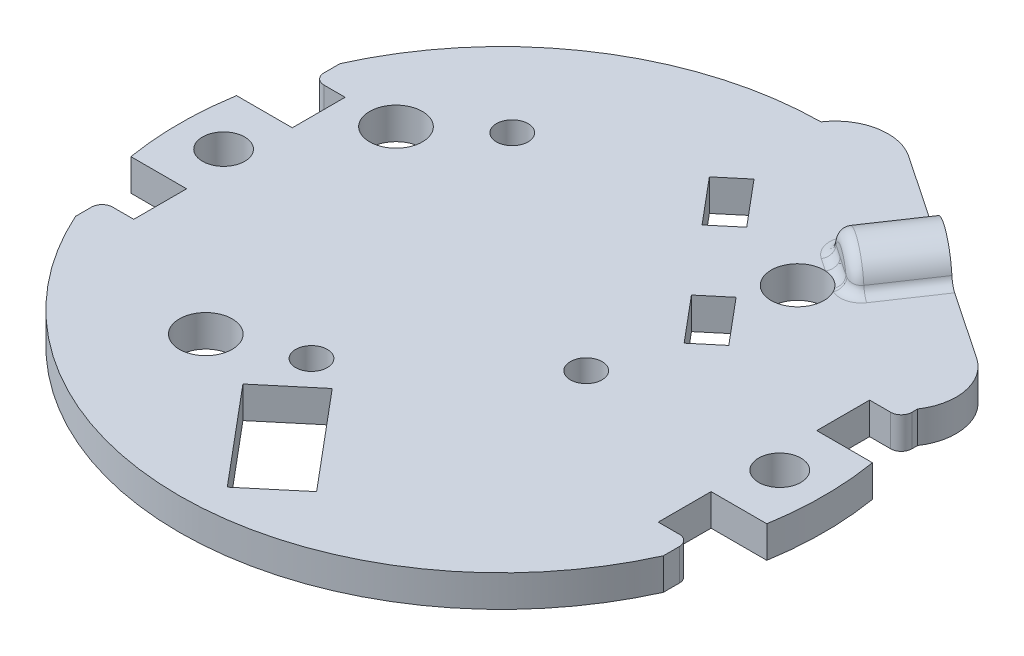
SolidWorks part; units mm, degrees
ref_plane "Alzado" through (0, 0, 0) normal (0, 0, 1) x (1, 0, 0)
ref_plane "Planta" through (0, 0, 0) normal (0, 1, 0) x (1, 0, 0)
ref_plane "Vista lateral" through (0, 0, 0) normal (1, 0, 0) x (0, 0, -1)
sketch "Croquis1" plane through (0, 0, 0) normal (0, 1, 0) x (1, 0, 0)
  circle A0 centre (0, 0) radius 30.5
extrude "Saliente-Extruir1" add sketch "Croquis1" along normal blind 3
sketch "Croquis5" plane through (0, 3, 0) normal (0, 1, 0) x (1, 0, 0)
  line L0 (0, 0) -> (0, 10)
  line L1 (28.8141, -5) -> (30.0874, -5)
  line L2 (28.8141, 5) -> (30.0874, 5)
  line L3 (-24.8141, 10) -> (-28.8141, 10)
  line L4 (24.8141, -5) -> (24.8141, -10)
  line L5 (-24.8141, -10) -> (-28.8141, -10)
  line L6 (24.8141, -5) -> (28.8141, -5)
  line L7 (24.8141, 5) -> (24.8141, 10)
  line L8 (-24.8141, 5) -> (-28.8141, 5)
  line L9 (-24.8141, 5) -> (-24.8141, 10)
  line L10 (-24.8141, -5) -> (-28.8141, -5)
  line L11 (-24.8141, -5) -> (-24.8141, -10)
  line L12 (24.8141, 5) -> (28.8141, 5)
  line L13 (24.8141, -10) -> (28.8141, -10)
  line L14 (24.8141, 10) -> (28.8141, 10)
  line L15 (-28.8141, 5) -> (-30.0874, 5)
  line L16 (-28.8141, -5) -> (-30.0874, -5)
  circle A1 centre (0, 0) radius 30.5 construction
  arc A2 (-28.8141, 10) -> (-30.0874, 5) centre (0, 0) ccw
  arc A3 (28.8141, 10) -> (28.8141, -10) centre (0, 0) cw
  arc A4 (-30.0874, -5) -> (-28.8141, -10) centre (0, 0) ccw
  arc A5 (30.0874, -5) -> (28.8141, -10) centre (0, 0) cw
  arc A6 (28.8141, 10) -> (30.0874, 5) centre (0, 0) cw
  circle M2 centre (0, 0) radius 30.5
extrude "Cortar-Extruir3" cut sketch "Croquis5" against normal blind 4 contours L11 L10 L8 L9 L3 L5 M2 | L15 L8 L9 L3 M2 | L14 L7 L12 L2 M2 | L4 L13 L1 L6 M2 region at (27.1844, 3, 7.3876) region at (27.1844, 3, -7.3876) region at (-27.1844, 3, 7.3876) region at (-27.1844, 3, -7.3876)
sketch "Croquis7" plane through (0, 3, 0) normal (0, 1, 0) x (1, 0, 0)
  line L0 (-8.1011, 29.1011) -> (9.5756, 8.0348)
  line L1 (9.5756, 8.0348) -> (27.2522, -13.0314)
  line L2 (-8.1011, 29.1011) -> (-27.2522, 13.0314)
  line L3 (27.2522, -13.0314) -> (8.1011, -29.1011)
  line L4 (8.1011, -29.1011) -> (-27.2522, 13.0314)
  line L5 (1.4284, 22.4114) -> (-0.8697, 20.4831)
  line L6 (1.4284, 22.4114) -> (4.6423, 18.5812)
  line L7 (4.6423, 18.5812) -> (2.3442, 16.6528)
  line L8 (2.3442, 16.6528) -> (-0.8697, 20.4831)
  line L9 (7.9686, 9.95) -> (11.1825, 6.1197)
  line L10 (8.1011, -29.1011) -> (5.53, -26.0369)
  line L11 (10.2667, 11.8783) -> (13.4807, 8.0481)
  line L12 (13.4807, 8.0481) -> (11.1825, 6.1197)
  line L13 (10.2667, 11.8783) -> (7.9686, 9.95)
  line L14 (5.53, -26.0369) -> (10.8923, -21.5374)
  line L15 (10.8923, -21.5374) -> (-19.3188, 14.4667)
  line L17 (-24.6811, 9.9672) -> (-19.3188, 14.4667)
  point P7 (-9.5756, -8.0348)
extrude "Cortar-Extruir5" cut sketch "Croquis7" against normal blind 4 contours L7 L6 L5 L0 | L11 L13 L0 L1 L12 region at (1.8863, 3, -19.5321) region at (10.7246, 3, -8.999)
sketch "Croquis8" plane through (0, 3, 0) normal (0, 1, 0) x (1, 0, 0)
  line L0 (-11.3137, 11.3137) -> (0, 0)
  line L2 (0, 0) -> (12, 0)
  line L3 (0, 0) -> (-11.3137, 11.3137)
  line L4 (12, 0) -> (12, 16)
  line L5 (0, 0) -> (-12, 0)
  line L6 (-12, 0) -> (-12, -16)
  line L10 (1.5586, -27.5246) -> (6.1549, -23.6679)
  line L11 (6.1549, -23.6679) -> (-1.5586, -14.4754)
  line L13 (-6.1549, -18.3321) -> (-1.5586, -14.4754)
  line L14 (1.5586, -27.5246) -> (-6.1549, -18.3321)
  circle A0 centre (0, 0) radius 30
  circle A1 centre (9, -1) radius 1.5
  circle A2 centre (-5, -13) radius 1.5
  circle A3 centre (-12, -16) radius 2.5
  circle A4 centre (-14, 15) radius 1.5
  circle A5 centre (12, 16) radius 2.5
  point P20 (-3.8567, -16.4037)
extrude "Cortar-Extruir6" cut sketch "Croquis8" against normal blind 10 contours L13 L10 L11 | A3 | L6 A3 | A3 L6 | A5 | L4 A5 | A5 L4 | L14 L10 L11 | L14 L11 | L13 L11 | A4 | L2 A1 | L2 A1 | A2 region at (10.2822, 3, -17.7178) region at (9, 3, -0.2032) region at (9, 3, 1.148) region at (-10.2822, 3, 14.2822) region at (0, 3, 21) region at (-5, 3, 13) region at (-14, 3, -15)
sketch "Croquis10" plane through (0, 3, 0) normal (0, 1, 0) x (1, 0, 0)
  line L0 (-24.8141, 10) -> (-27.8141, 10)
  line L2 (-24.8141, 10) -> (-28.8141, 10) construction
  line L4 (-27.8141, 10) -> (-27.8141, 12.5151)
  line L6 (-27.8141, 10) -> (-28.8141, 10)
  line L14 (-27.8141, -10) -> (-28.8141, -10)
  line L15 (-27.8141, -10) -> (-27.8141, -12.5151)
  line L16 (27.8141, -10) -> (27.8141, -12.5151)
  line L17 (27.8141, -10) -> (28.8141, -10)
  line L21 (27.8141, 10) -> (28.8141, 10)
  line L22 (27.8141, 10) -> (27.8141, 12.5151)
  line L23 (24.8141, 10) -> (27.8141, 10)
  circle A0 centre (-26.3141, 0) radius 2
  circle A1 centre (26.3141, 0) radius 2
  arc A2 (28.8141, 10) -> (-28.8141, 10) centre (0, 0) ccw construction
  arc A5 (-27.8141, 12.5151) -> (-28.8141, 10) centre (0, 0) ccw
  arc A7 (-27.8141, -12.5151) -> (-28.8141, -10) centre (0, 0) cw
  arc A8 (27.8141, -12.5151) -> (28.8141, -10) centre (0, 0) ccw
  arc A10 (27.8141, 12.5151) -> (28.8141, 10) centre (0, 0) cw
  line M13 (24.8141, 10) -> (28.8141, 10)
  arc M14 (28.8141, 10) -> (-28.8141, 10) centre (0, 0) ccw
  line M15 (-28.8141, 10) -> (-24.8141, 10)
  line M21 (-24.8141, -10) -> (-28.8141, -10)
  arc M22 (-28.8141, -10) -> (28.8141, -10) centre (0, 0) ccw
  line M23 (28.8141, -10) -> (24.8141, -10)
extrude "Cortar-Extruir8" cut sketch "Croquis10" against normal blind 3 contours L15 M21 M22 | L4 M15 M14 | L16 M23 M22 | L22 M13 M14 | A0 | A1 | L22 A10 L21 region at (-28.1547, 3, -10.8559) region at (28.1547, 3, -10.8559) region at (-28.1547, 3, 10.8559) region at (28.1547, 3, 10.8559) region at (-26.3141, 3, 0) region at (26.3141, 3, 0)
sketch "Croquis11" plane through (0, 3, 0) normal (0, 1, 0) x (1, 0, 0)
  line L0 (0, 0) -> (-20, 0)
  line L1 (-20, 0) -> (-20, 10)
  line L2 (0, 0) -> (0, 4.5949)
  line L3 (29.8013, 10.2046) -> (-1.7022, 31.454)
  circle A0 centre (-20, 10) radius 2.5
  circle A5 centre (0, 0) radius 31.5
  line M20 (27.8141, 10) -> (27.8141, 12.5151)
  arc M21 (27.8141, 12.5151) -> (-27.8141, 12.5151) centre (0, 0) ccw
extrude "Cortar-Extruir9" cut sketch "Croquis11" against normal blind 3 contours L3 M20 M21 | A0 region at (15.2326, 3, -22.6507) region at (-18.2822, 3, -8.2822)
sketch "Croquis13" plane through (14.0495, 0, -20.8293) normal (0.5592, 0, -0.829) x (-0.829, 0, -0.5592)
  line L1 (-16.603, 0) -> (17.2916, 0)
  line L2 (-16.603, 0) -> (-16.603, 3)
  line L3 (-16.603, 3) -> (17.2916, 3)
  line L4 (17.2916, 0) -> (17.2916, 3)
extrude "Saliente-Extruir2" add sketch "Croquis13" along normal blind 6
sketch "Croquis14" plane through (17.4047, 0, -25.8035) normal (0.5592, 0, -0.829) x (-0.829, 0, -0.5592)
  circle A0 centre (0.0043, 3) radius 3
extrude "Saliente-Extruir3" add sketch "Croquis14" against normal blind 8
sketch "Croquis17" plane through (17.4047, 0, -25.8035) normal (0.5592, 0, -0.829) x (-0.829, 0, -0.5592)
  circle A0 centre (0.0043, 3) radius 1.5
extrude "Cortar-Extruir10" cut sketch "Croquis17" against normal blind 7
sketch "Croquis19" plane through (17.4047, 0, -25.8035) normal (0.5592, 0, -0.829) x (-0.829, 0, -0.5592)
  line L0 (3.0043, 3) -> (17.2916, 3)
  line L1 (17.2916, 3) -> (17.2916, 0)
  line L2 (17.2916, 0) -> (-16.603, 0)
  line L3 (-16.603, 0) -> (-16.603, 3)
  line L4 (-16.603, 3) -> (-2.9957, 3)
  arc A0 (3.0043, 3) -> (-2.9957, 3) centre (0.0043, 3) ccw
extrude "Cortar-Extruir11" cut sketch "Croquis19" against normal blind 6
sketch "Croquis20" plane through (14.0495, 0, -20.8293) normal (0.5592, 0, -0.829) x (-0.829, 0, -0.5592)
  circle A0 centre (0.0043, 3) radius 1.5
  circle A1 centre (0.0043, 3) radius 3
extrude "Saliente-Extruir4" add sketch "Croquis20" along normal blind 5
fillet "Redondeo1" radius 1 1 edges at (12.9276, 6, -19.1736)
sketch "Croquis21" plane through (0, 3, 0) normal (0, 1, 0) x (1, 0, 0)
  line L0 (7.9686, 9.95) -> (10.2667, 11.8783)
  line L1 (7.9686, 9.95) -> (7.7758, 10.1798)
  line L2 (10.2667, 11.8783) -> (10.0739, 12.1081)
  line L3 (7.7758, 10.1798) -> (10.0739, 12.1081)
  line L4 (11.1825, 6.1197) -> (13.4807, 8.0481)
  line L5 (11.1825, 6.1197) -> (11.3754, 5.8899)
  line L6 (13.4807, 8.0481) -> (13.6735, 7.8183)
  line L7 (11.3754, 5.8899) -> (13.6735, 7.8183)
  line L8 (2.3442, 16.6528) -> (4.6423, 18.5812)
  line L9 (2.3442, 16.6528) -> (2.537, 16.423)
  line L10 (4.6423, 18.5812) -> (4.8352, 18.3514)
  line L11 (2.537, 16.423) -> (4.8352, 18.3514)
  line L12 (-0.8697, 20.4831) -> (1.4284, 22.4114)
  line L13 (-0.8697, 20.4831) -> (-1.0626, 20.7129)
  line L14 (1.4284, 22.4114) -> (1.2356, 22.6412)
  line L15 (-1.0626, 20.7129) -> (1.2356, 22.6412)
extrude "Cortar-Extruir12" cut sketch "Croquis21" against normal blind 3
fillet "Redondeo3" radius 1 4 edges at (-27.8141, 1.5, 10) (-27.8141, 1.5, -10) (27.8141, 1.5, 10) (27.8141, 1.5, -10)
sketch "Croquis22" plane through (14.0495, 0, -20.8293) normal (0.5592, 0, -0.829) x (-0.829, 0, -0.5592)
  line L0 (3.0043, 3) -> (17.2916, 3)
  line L1 (17.2916, 3) -> (17.2916, 0)
  line L2 (17.2916, 0) -> (-16.603, 0)
  line L3 (-16.603, 0) -> (-16.603, 3)
  line L4 (-16.603, 3) -> (-2.9957, 3)
  arc A0 (-2.9957, 3) -> (3.0043, 3) centre (0.0043, 3) ccw
  line M1 (17.2916, 3) -> (3.0043, 3)
  arc M2 (3.0043, 3) -> (0.0043, 0) centre (0.0043, 3) cw
  line M3 (0.0043, 0) -> (17.2916, 0)
  line M4 (17.2916, 0) -> (17.2916, 3)
extrude "Saliente-Extruir5" add sketch "Croquis22" along normal up to surface (5 mm away) contours A0 L4 L3 L2 | M4 M1 M2 M3 region at (21.8937, 1.4625, -15.5384) region at (5.9158, 1.4642, -26.3156) up to face at (14.3548, 3, -26.6545)
chamfer "Chaflán1" distance 1 angle 45 1 edges at (15.5984, 3, -25.8157)
fillet "Redondeo6" radius 1 5 edges at (10.8471, 3, -20.9303) (12.9276, 3, -19.1736) (15.3357, 3, -17.9027) (12.6772, 3, -24.1674) (17.6515, 3, -20.8122)
fillet "Redondeo7" radius 5 2 edges at (2.5101, 1.5, -34.6438) (30.61, 1.5, -15.6902)
